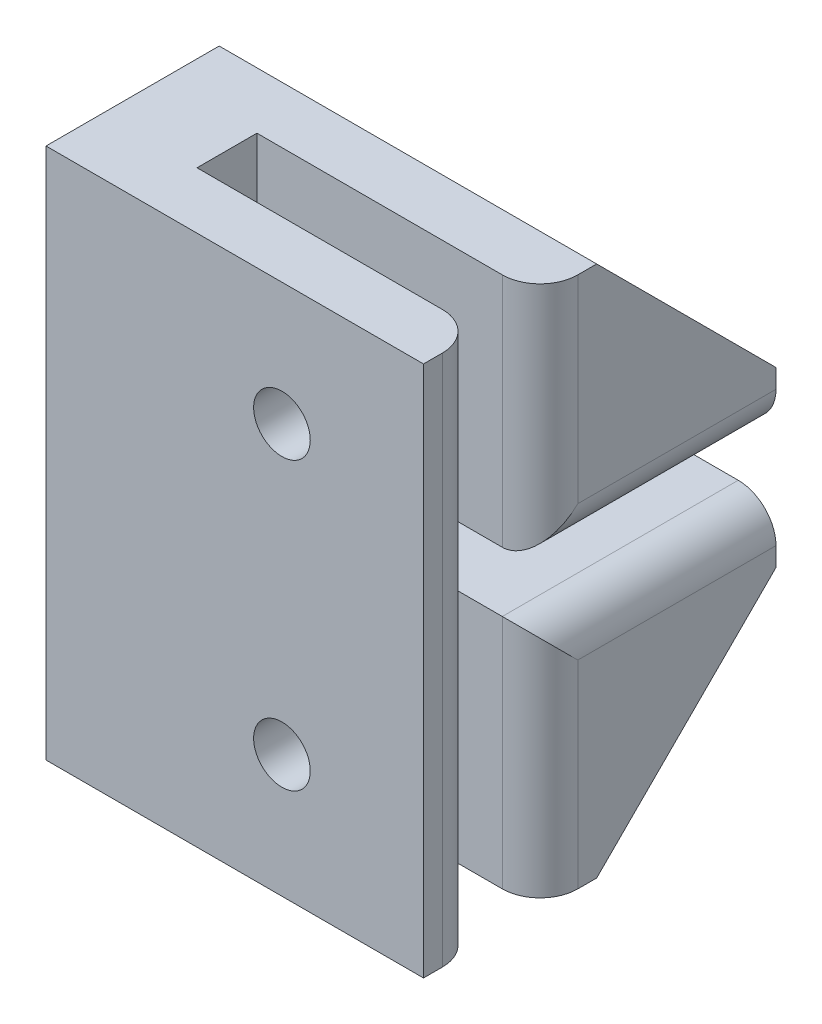
SolidWorks part; units mm, degrees
ref_plane "Front Plane" through (0, 0, 0) normal (0, 0, 1) x (1, 0, 0)
ref_plane "Top Plane" through (0, 0, 0) normal (0, 1, 0) x (1, 0, 0)
ref_plane "Right Plane" through (0, 0, 0) normal (1, 0, 0) x (0, 0, -1)
sketch "Sketch1" plane through (0, 0, 0) normal (1, 0, 0) x (0, 0, -1)
  line L0 (0, 0) -> (0, -12.5) construction
  line L1 (0, -12.5) -> (-3.175, -12.5)
  line L2 (-3.175, -12.5) -> (-3.175, 3.175) construction
  line L3 (-3.175, 3.175) -> (12.5, 3.175) construction
  line L4 (12.5, 3.175) -> (12.5, 0)
  line L5 (12.5, 0) -> (0, 0) construction
  line L6 (0, -12.5) -> (3, -12.5)
  line L7 (3, -12.5) -> (12.5, -3)
  line L8 (12.5, -3) -> (12.5, 0)
  line L9 (12.5, 3.175) -> (12.5, 6.175)
  line L11 (-6.175, 15.675) -> (-6.175, -12.5)
  line L12 (-6.175, -12.5) -> (-3.175, -12.5)
  line L13 (-3.175, 3.175) -> (-3.175, 15.675) construction
  line L14 (-3.175, 15.675) -> (0, 15.675)
  line L15 (0, 15.675) -> (0, 3.175) construction
  line L16 (-6.175, 15.675) -> (-3.175, 15.675)
  line L17 (0, 15.675) -> (3, 15.675)
  line L18 (3, 15.675) -> (12.5, 6.175)
  dimension "D1" = 3.175
  dimension "D2" = 3.175
  dimension "D3" = 12.5
  dimension "D4" = 12.5
  dimension "D5" = 3
  dimension "D6" = 3
  dimension "D7" = 3
  dimension "D8" = 3
  dimension "D9" = 12.5
  dimension "D10" = 3
extrude "Boss-Extrude1" add sketch "Sketch1" along normal blind 20
sketch "Sketch2" plane through (20, 0, 0) normal (1, 0, 0) x (0, 0, -1)
  line L0 (-3.175, -12.5) -> (0, -12.5)
  line L1 (0, -12.5) -> (0, 0)
  line L2 (0, 0) -> (12.5, 0)
  line L3 (12.5, 0) -> (12.5, 3.175)
  line L4 (12.5, 3.175) -> (0, 3.175)
  line L5 (-3.175, 3.175) -> (-3.175, -12.5)
  line L6 (-3.175, 3.175) -> (-3.175, 15.675)
  line L7 (3, 15.675) -> (-6.175, 15.675) construction
  line L8 (-3.175, 15.675) -> (0, 15.675)
  line L9 (0, 15.675) -> (0, 3.175)
extrude "Cut-Extrude1" cut sketch "Sketch2" against normal blind 15
fillet "Fillet1" radius 2 5 edges at (20, 1.5875, 3.175) (20, -6.25, 0) (20, 0, -6.25) (20, 3.175, -6.25) (20, 9.425, 0)
sketch "Sketch5" plane through (0, 0, 6.175) normal (0, 0, 1) x (1, 0, 0)
  line L0 (5, 15.675) -> (5, -12.5) construction
  line L1 (20, 15.675) -> (0, 15.675) construction
  line L2 (20, -12.5) -> (0, -12.5) construction
  line L3 (0, 15.675) -> (0, -12.5) construction
  line L4 (5, 9.175) -> (20, 9.175) construction
  line L5 (20, 15.675) -> (20, -12.5) construction
  line L6 (5, -6) -> (20, -6) construction
  line L7 (5, 3.175) -> (18, 3.175) construction
  line L8 (5, 0) -> (18, 0) construction
  circle A0 centre (12.5, 9.175) radius 1.5
  circle A1 centre (12.5, -6) radius 1.5
  dimension "D4" = 3
  dimension "D5" = 3
  dimension "D1" = 5
  dimension "D2" = 6
  dimension "D3" = 6
extrude "Cut-Extrude4" cut sketch "Sketch5" against normal through all
